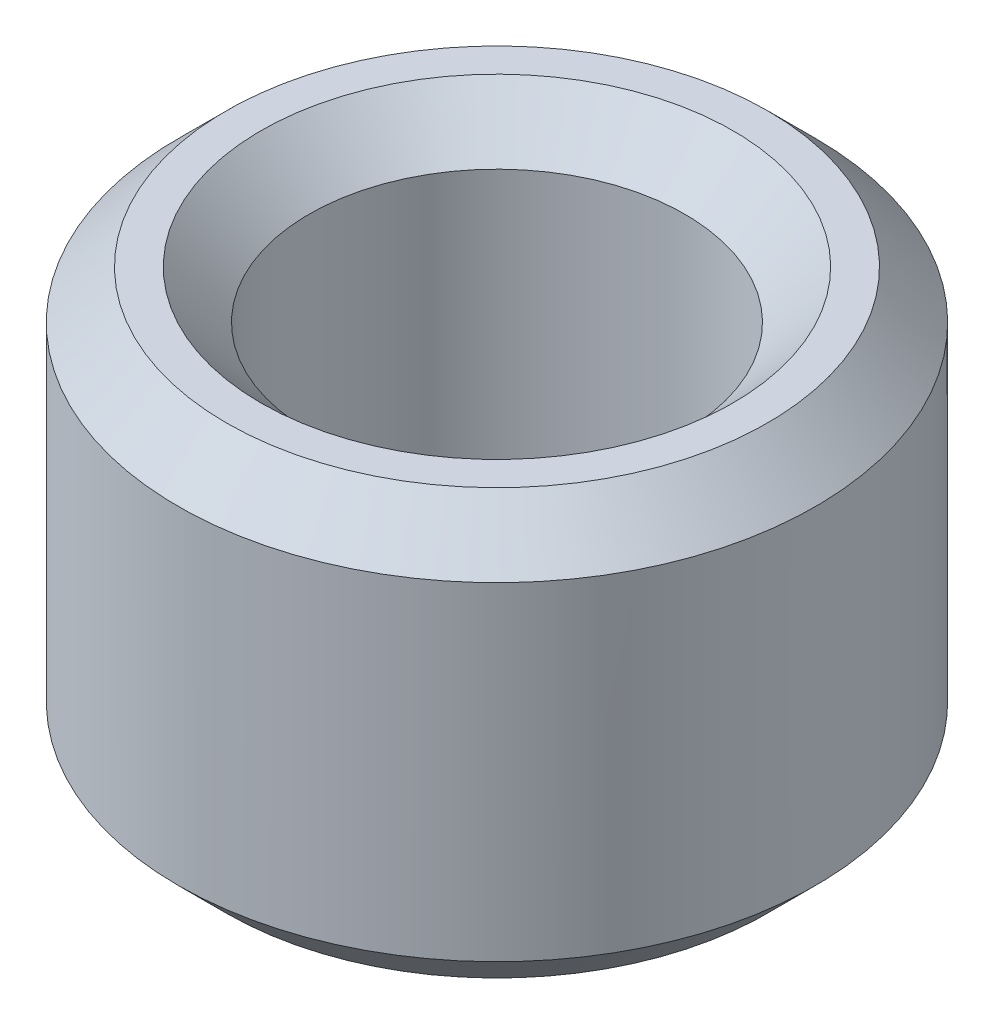
SolidWorks part; units mm, degrees
ref_plane "Front Plane" through (0, 0, 0) normal (0, 0, 1) x (1, 0, 0)
ref_plane "Top Plane" through (0, 0, 0) normal (0, 1, 0) x (1, 0, 0)
ref_plane "Right Plane" through (0, 0, 0) normal (1, 0, 0) x (0, 0, -1)
sketch "Sketch1" plane through (0, 0, 0) normal (0, 1, 0) x (1, 0, 0)
  circle A0 centre (0, 0) radius 12.5
  dimension "SLEEVE_OD" = 25
extrude "Boss-Extrude1" add sketch "Sketch1" along normal blind 16.6557
sketch "Sketch2" plane through (0, 0, 0) normal (0, 1, 0) x (1, 0, 0)
  circle A0 centre (0, 0) radius 7.3647
  dimension "BORE_D" = 14.7293
extrude "Cut-Extrude1" cut sketch "Sketch2" along normal through all
chamfer "Chamfer1" distance 1.8903 angle 45 4 edges at (0, 16.6557, 7.3647) (0, 0, 7.3647) (0, 0, 12.5) (0, 16.6557, 12.5)
